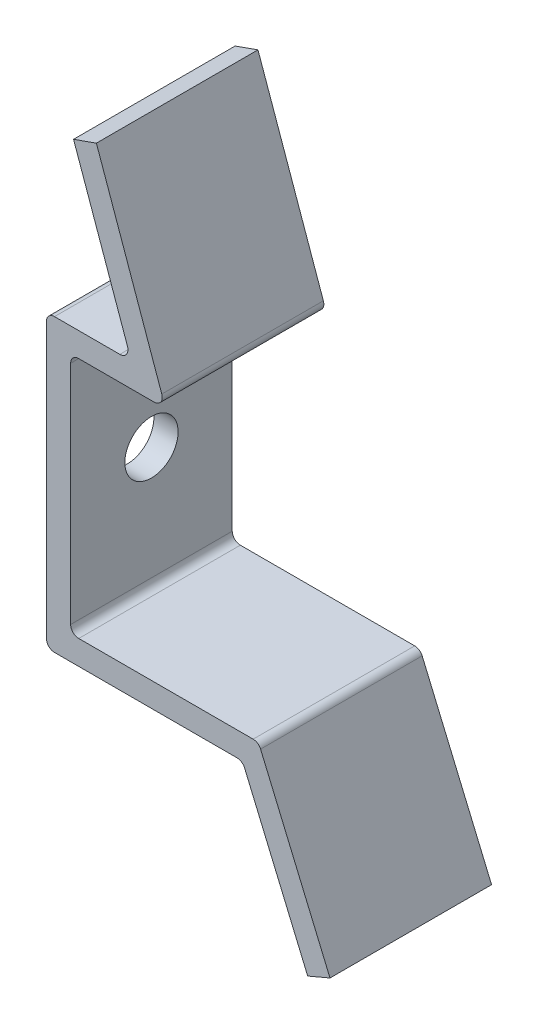
SolidWorks part; units mm, degrees
ref_plane "Спереди" through (0, 0, 0) normal (0, 0, 1) x (1, 0, 0)
ref_plane "Сверху" through (0, 0, 0) normal (0, 1, 0) x (1, 0, 0)
ref_plane "Справа" through (0, 0, 0) normal (1, 0, 0) x (0, 0, -1)
sketch "Эскиз1" plane through (0, 0, 0) normal (0, 0, 1) x (1, 0, 0)
  line L0 (0, 17) -> (0, -17)
  line L1 (1, -18) -> (23.6025, -18)
  line L2 (24.523, -18.6093) -> (32.3376, -37.0194)
  line L3 (32.3376, -37.0194) -> (35.0991, -35.8472)
  line L4 (35.0991, -35.8472) -> (26.5086, -15.6093)
  line L5 (25.5881, -15) -> (4, -15)
  line L6 (3, -14) -> (3, 14)
  line L7 (4, 15) -> (13.335, 15)
  line L8 (14.2777, 16.3338) -> (6.1846, 39.1881)
  line L9 (6.1846, 39.1881) -> (3.3566, 38.1866)
  line L12 (3.3566, 38.1866) -> (10.0328, 19.3338)
  line L13 (9.0901, 18) -> (1, 18)
  arc A0 (10.0328, 19.3338) -> (9.0901, 18) centre (9.0901, 19) cw
  arc A1 (13.335, 15) -> (14.2777, 16.3338) centre (13.335, 16) ccw
  arc A2 (26.5086, -15.6093) -> (25.5881, -15) centre (25.5881, -16) ccw
  arc A3 (23.6025, -18) -> (24.523, -18.6093) centre (23.6025, -19) cw
  arc A4 (0, -17) -> (1, -18) centre (1, -17) ccw
  arc A5 (4, -15) -> (3, -14) centre (4, -14) cw
  arc A6 (3, 14) -> (4, 15) centre (4, 14) cw
  arc A7 (0, 17) -> (1, 18) centre (1, 17) cw
  point P17 (14.75, 15)
  point P20 (26.25, -15)
  point P29 (3, 15)
  dimension "D12" = 1
  dimension "D1" = 3
  dimension "D2" = 3
  dimension "D3" = 3
  dimension "D4" = 30
  dimension "D5" = 15
  dimension "D6" = 3
  dimension "D7" = 3
  dimension "D8" = 70.5
  dimension "D9" = 23.25
  dimension "D10" = 11.75
  dimension "D11" = 113
  dimension "D13" = 20
  dimension "D14" = 20
extrude "Бобышка-Вытянуть1" add sketch "Эскиз1" along normal blind 10 and the other way blind 10
hole_wizard "Отверстие с зазором M61" positions "Трехмерный эскиз1" profile "Эскиз2" hole size "M6" standard "ISO" end condition through all
sketch3d "Трехмерный эскиз1"
  point P11 (0, 0, 0)
sketch "Эскиз2" plane through (0, 0, 0) normal (0, 1, 0) x (0, 0, 1)
  line L0 (0, 0) -> (0, 35.0991)
  line L1 (0, 35.0991) -> (3.3, 35.0991)
  line L2 (3.3, 35.0991) -> (3.3, 0)
  line L5 (3.3, 0) -> (0, 0)
  line L11 (0, -6.35) -> (0, 107.95) construction
  dimension "Диаметр сквозного отверстия" = 6.6
  dimension "Глубина сквозного отверстия" = 35.0991
